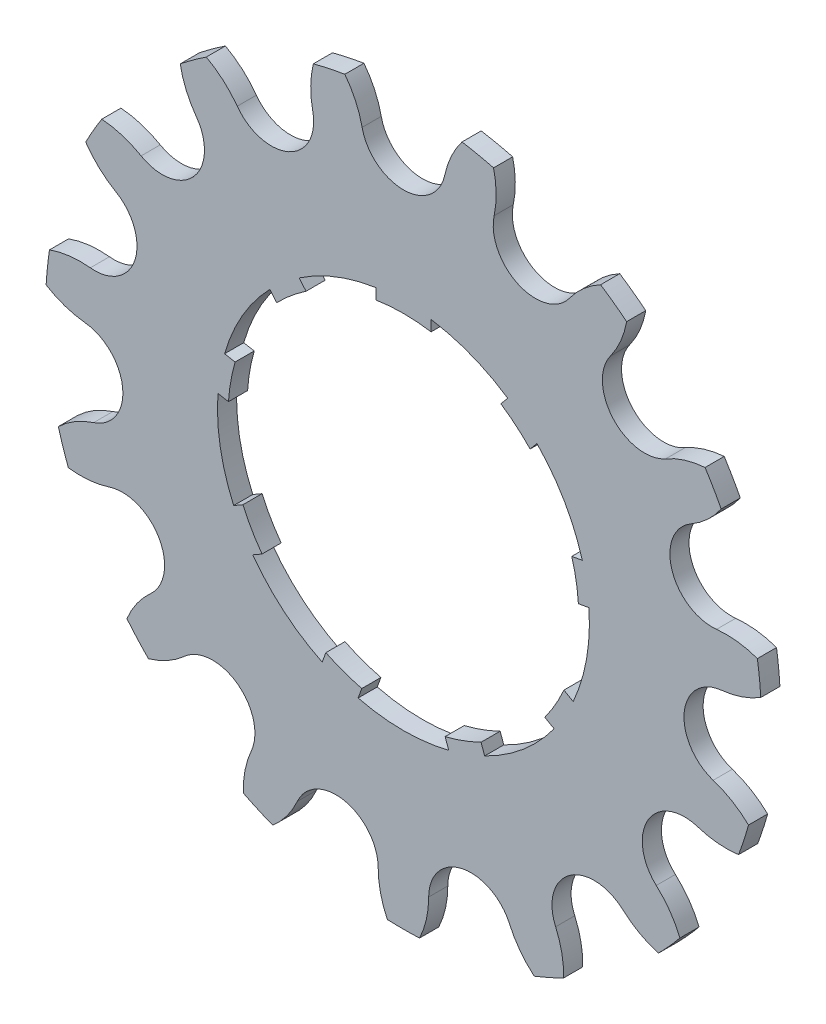
SolidWorks part; units mm, degrees
ref_plane "Alzado" through (0, 0, 0) normal (0, 0, 1) x (1, 0, 0)
ref_plane "Planta" through (0, 0, 0) normal (0, 1, 0) x (1, 0, 0)
ref_plane "Vista lateral" through (0, 0, 0) normal (1, 0, 0) x (0, 0, -1)
sketch "Sk_Disco" plane through (0, 0, 0) normal (0, 0, 1) x (1, 0, 0)
  line L0 (2.6, 17.3058) -> (2.6, 16.2939)
  line L1 (-2.6, 16.2939) -> (-2.6, 17.3058)
  line L2 (-9.8102, 14.4917) -> (-9.1638, 13.7213)
  line L3 (-11.9216, 11.4073) -> (-12.568, 12.1777)
  line L4 (-16.8302, 4.7954) -> (-15.8398, 4.6207)
  line L5 (-16.4649, 1.0754) -> (-17.4553, 1.2501)
  line L6 (-15.9751, -7.1447) -> (-15.1041, -6.6419)
  line L7 (-13.3041, -9.7596) -> (-14.1751, -10.2624)
  line L8 (-7.6451, -15.7418) -> (-7.3011, -14.7968)
  line L9 (-3.9182, -16.028) -> (-4.2622, -16.973)
  line L10 (4.2622, -16.973) -> (3.9182, -16.028)
  line L11 (7.3011, -14.7968) -> (7.6451, -15.7418)
  line L12 (14.1751, -10.2624) -> (13.3041, -9.7596)
  line L13 (15.1041, -6.6419) -> (15.9751, -7.1447)
  line L14 (17.4553, 1.2501) -> (16.4649, 1.0754)
  line L15 (15.8398, 4.6207) -> (16.8302, 4.7954)
  line L16 (12.568, 12.1777) -> (11.9216, 11.4073)
  line L17 (9.1638, 13.7213) -> (9.8102, 14.4917)
  circle A0 centre (0, 0) radius 33.6844
  arc A1 (2.6, 16.2939) -> (-2.6, 16.2939) centre (0, 0) ccw
  arc A2 (-2.6, 17.3058) -> (-9.8102, 14.4917) centre (0, 0) ccw
  arc A3 (-9.1638, 13.7213) -> (-11.9216, 11.4073) centre (0, 0) ccw
  arc A4 (-12.568, 12.1777) -> (-16.8302, 4.7954) centre (0, 0) ccw
  arc A5 (-15.8398, 4.6207) -> (-16.4649, 1.0754) centre (0, 0) ccw
  arc A6 (-17.4553, 1.2501) -> (-15.9751, -7.1447) centre (0, 0) ccw
  arc A7 (-15.1041, -6.6419) -> (-13.3041, -9.7596) centre (0, 0) ccw
  arc A8 (-14.1751, -10.2624) -> (-7.6451, -15.7418) centre (0, 0) ccw
  arc A9 (-7.3011, -14.7968) -> (-3.9182, -16.028) centre (0, 0) ccw
  arc A10 (-4.2622, -16.973) -> (4.2622, -16.973) centre (0, 0) ccw
  arc A11 (3.9182, -16.028) -> (7.3011, -14.7968) centre (0, 0) ccw
  arc A12 (7.6451, -15.7418) -> (14.1751, -10.2624) centre (0, 0) ccw
  arc A13 (13.3041, -9.7596) -> (15.1041, -6.6419) centre (0, 0) ccw
  arc A14 (15.9751, -7.1447) -> (17.4553, 1.2501) centre (0, 0) ccw
  arc A15 (16.4649, 1.0754) -> (15.8398, 4.6207) centre (0, 0) ccw
  arc A16 (16.8302, 4.7954) -> (12.568, 12.1777) centre (0, 0) ccw
  arc A17 (11.9216, 11.4073) -> (9.1638, 13.7213) centre (0, 0) ccw
  arc A18 (9.8102, 14.4917) -> (2.6, 17.3058) centre (0, 0) ccw
  dimension "D1" = 67.3688
extrude "Disco" add sketch "Sk_Disco" along normal blind 1.8
sketch "Sk_Hueco" plane through (0, 0, 0) normal (0, 0, 1) x (1, 0, 0)
  line L0 (0, 0) -> (0, 30.5418) construction
  line L1 (0, 0) -> (-12.4225, 27.9013) construction
  line L2 (0, 0) -> (12.4225, 27.9013) construction
  line L3 (0, 30.5418) -> (-12.4225, 27.9013) construction
  line L4 (0, 30.5418) -> (12.4225, 27.9013) construction
  arc A0 (-3.8881, 29.7154) -> (3.8881, 29.7154) centre (0, 30.5418) ccw
  arc A1 (-3.8881, 29.7154) -> (-7.2631, 34.9374) centre (-12.4225, 27.9013) ccw
  arc A2 (7.2631, 34.9374) -> (3.8881, 29.7154) centre (12.4225, 27.9013) ccw
  arc A3 (7.2631, 34.9374) -> (-7.2631, 34.9374) centre (0, 0) ccw
  dimension "D6" = 3.975
  dimension "D7" = 35.6844
  dimension "D1" = 30.5418
  dimension "D2" = 30.5418
  dimension "D3" = 30.5418
  dimension "D4" = 24
  dimension "D5" = 24
extrude "Hueco_diente" cut sketch "Sk_Hueco" along normal through all
ref_axis "Eje_pinon" through (0, 0, -0.09) along (0, 0, 1)
pattern_circular "Matriz_dientes" count 15 over 360 about axis through (0, 0, -0.09) along (0, 0, 1) of "Hueco_diente"
equation "\"Z\"= 15"
equation "\"p\"= 12.7"
equation "\"Dr\"= 7.75"
equation "\"e\"= 1.8"
equation "\"D\"= \"p\" / sin ( 180 / \"Z\" )"
equation "\"De\"= \"p\" * ( 0.6 + 1 / tan ( 180 / \"Z\" ) )"
equation "\"Di\"= \"D\" - \"Dr\""
equation "\"Ang\"= 360 / \"Z\""
equation "\"D1@Sk_Disco\" = \"De\""
equation "\"D1@Disco\" = \"e\""
equation "\"D1@Sk_Hueco\" = \"D\" / 2"
equation "\"D2@Sk_Hueco\" = \"D\" / 2"
equation "\"D3@Sk_Hueco\" = \"D\" / 2"
equation "\"D4@Sk_Hueco\" = \"Ang\""
equation "\"D5@Sk_Hueco\" = \"Ang\""
equation "\"D6@Sk_Hueco\" = \"Dr\" / 2 + 0.1"
equation "\"D7@Sk_Hueco\" = \"De\" / 2 + 2"
equation "\"D1@Matriz_dientes\" = \"Z\""
